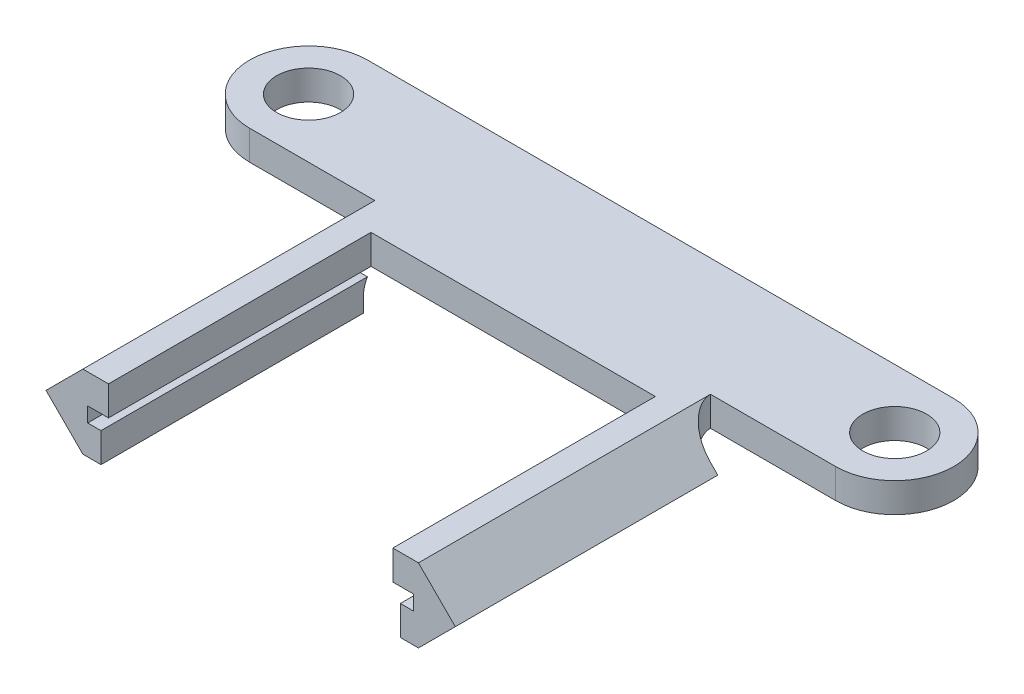
SolidWorks part; units mm, degrees
ref_plane "Front Plane" through (0, 0, 0) normal (0, 0, 1) x (1, 0, 0)
ref_plane "Top Plane" through (0, 0, 0) normal (0, 1, 0) x (1, 0, 0)
ref_plane "Right Plane" through (0, 0, 0) normal (1, 0, 0) x (0, 0, -1)
sketch "Sketch1" plane through (0, 0, 0) normal (0, 0, 1) x (1, 0, 0)
  line L0 (0.8255, 1.27) -> (0, 1.27)
  line L1 (0, 0) -> (0.8255, 0) construction
  line L2 (0, 0) -> (0, 1.27) construction
  line L3 (0, 1.27) -> (0.8255, 1.27) construction
  line L4 (0.8255, 0) -> (0.8255, 1.27) construction
  line L5 (0.4127, 1.27) -> (0.4128, 0) construction
  line L6 (0, 0.635) -> (0.8255, 0.635) construction
  line L7 (0.8255, 0) -> (0, 0)
  line L8 (0, 0) -> (-0.635, 0.635) construction
  line L9 (-0.635, 0.635) -> (0, 1.27) construction
  line L10 (25.9715, 0) -> (26.797, 0)
  line L11 (0.8255, 1.27) -> (25.9715, 1.27)
  line L12 (0.8255, 1.27) -> (0.8255, 0) construction
  line L13 (0.8255, 0) -> (25.9715, 0)
  line L14 (25.9715, 1.27) -> (25.9715, 0) construction
  line L15 (13.3985, 0) -> (13.3985, 1.27) construction
  line L16 (0.8255, 0.635) -> (25.9715, 0.635) construction
  line L17 (26.797, 0) -> (27.432, 0.635) construction
  line L18 (25.9715, 1.27) -> (26.797, 1.27)
  line L19 (27.432, 0.635) -> (26.797, 1.27) construction
  line L20 (-4.2271, 0.635) -> (-1.0521, 3.81)
  line L21 (0.8255, 3.81) -> (-1.0521, 3.81)
  line L22 (0.8255, 3.81) -> (25.9715, 3.81)
  line L23 (25.9715, 3.81) -> (27.8491, 3.81)
  line L24 (31.0241, 0.635) -> (27.8491, 3.81)
  line L25 (27.8491, -2.54) -> (31.0241, 0.635)
  line L26 (25.9715, -2.54) -> (27.8491, -2.54)
  line L27 (0.8255, -2.54) -> (25.9715, -2.54)
  line L28 (0.8255, -2.54) -> (-1.0521, -2.54)
  line L29 (-1.0521, -2.54) -> (-4.2271, 0.635)
  line L30 (0, 1.27) -> (-0.635, 1.27)
  line L31 (-0.635, 1.27) -> (-0.635, 0)
  line L32 (-0.635, 0) -> (0, 0)
  line L33 (26.797, 1.27) -> (27.432, 1.27)
  line L34 (27.432, 1.27) -> (27.432, 0)
  line L35 (27.432, 0) -> (26.797, 0)
  point P287 (13.3985, 0.635)
  point P500 (0.4127, 0.635)
  dimension "D1" = 1.27
  dimension "D2" = 0.8255
  dimension "D3" = 45
  dimension "D4" = 25.146
  dimension "D5" = 2.54
extrude "Boss-Extrude1" add sketch "Sketch1" along normal blind 22.606
sketch "Sketch2" plane through (0, 0, 22.606) normal (0, 0, 1) x (1, 0, 0)
  line L5 (13.3985, 0) -> (13.3985, -2.54) construction
  line L6 (-0.635, 0) -> (27.432, 0) construction
  line L7 (-1.0521, -2.54) -> (27.8491, -2.54) construction
  line L9 (0.508, 0) -> (26.289, 0)
  line L10 (0.508, 0) -> (0.508, -2.54)
  line L11 (0.508, -2.54) -> (26.289, -2.54)
  line L12 (26.289, 0) -> (26.289, -2.54)
  line L13 (13.3985, -2.54) -> (13.3985, 0) construction
  line L14 (0.508, -1.27) -> (26.289, -1.27) construction
  point P218 (13.3985, -1.27)
  dimension "D1" = 0.508
extrude "Cut-Extrude1" cut sketch "Sketch2" against normal blind 22.606
sketch "Sketch5" plane through (0, 0, 0) normal (0, 0, -1) x (-1, 0, 0)
  line L12 (-31.0241, 0.635) -> (-27.432, 0.635)
  line L13 (-27.432, 0.635) -> (-27.432, 1.27)
  line L14 (-27.432, 1.27) -> (0.635, 1.27)
  line L15 (0.635, 1.27) -> (0.635, 0.635)
  line L16 (0.635, 1.27) -> (0.635, 0) construction
  line L17 (0.635, 0.635) -> (4.2271, 0.635)
  line L18 (4.2271, 0.635) -> (1.0521, 3.81)
  line L19 (1.0521, 3.81) -> (-27.8491, 3.81)
  line L20 (-27.8491, 3.81) -> (-31.0241, 0.635)
extrude "Boss-Extrude2" add sketch "Sketch5" along normal blind 12.7
sketch "Sketch3" plane through (0, 3.81, 0) normal (0, 1, 0) x (1, 0, 0)
  line L0 (13.3985, 0) -> (13.3985, -22.606) construction
  line L1 (27.8491, 0) -> (-1.0521, 0) construction
  line L2 (27.8491, -22.606) -> (-1.0521, -22.606) construction
  line L3 (6.1023, -15.0622) -> (2.9845, -15.0622) construction
  line L4 (1.1557, 0) -> (25.6413, 0) construction
  line L5 (1.1557, 0) -> (1.1557, -22.606) construction
  line L6 (1.1557, -22.606) -> (25.6413, -22.606) construction
  line L7 (25.6413, 0) -> (25.6413, -22.606) construction
  line L8 (13.3985, -22.606) -> (13.3985, 0) construction
  line L9 (1.1557, -11.303) -> (25.6413, -11.303) construction
  line L10 (6.1023, 0) -> (20.6947, 0) construction
  line L11 (6.1023, 0) -> (6.1023, -15.0622) construction
  line L12 (6.1023, -15.0622) -> (20.6947, -15.0622) construction
  line L13 (20.6947, 0) -> (20.6947, -15.0622) construction
  line L14 (13.3985, -15.0622) -> (13.3985, 0) construction
  line L15 (6.1023, -7.5311) -> (20.6947, -7.5311) construction
  line L16 (2.9845, 0) -> (23.8125, 0) construction
  line L17 (2.9845, 0) -> (2.9845, -22.606) construction
  line L18 (2.9845, -22.606) -> (23.8125, -22.606) construction
  line L19 (23.8125, 0) -> (23.8125, -22.606) construction
  line L20 (13.3985, -22.606) -> (13.3985, 0) construction
  line L21 (2.9845, -11.303) -> (23.8125, -11.303) construction
  line L22 (2.9845, -15.0622) -> (2.9845, 0) construction
  line L23 (2.9845, 0) -> (1.1557, 0)
  line L24 (1.1557, 0) -> (1.1557, -22.606)
  line L25 (1.1557, -22.606) -> (25.6413, -22.606)
  line L26 (25.6413, -22.606) -> (25.6413, 0)
  line L27 (25.6413, 0) -> (23.8125, 0)
  line L28 (23.8125, 0) -> (23.8125, -15.0622) construction
  line L29 (23.8125, -15.0622) -> (20.6947, -15.0622) construction
  line L32 (6.1023, 0) -> (20.6947, 0)
  line L33 (2.9845, 0) -> (6.1023, 0)
  line L34 (20.6947, 0) -> (23.8125, 0)
  point P250 (13.3985, -11.303)
  point P383 (13.3985, -7.5311)
  point P386 (13.3985, -11.303)
  dimension "D1" = 24.4856
  dimension "D2" = 14.5923
  dimension "D3" = 15.0622
  dimension "D4" = 20.828
extrude "Cut-Extrude4" cut sketch "Sketch3" against normal up to vertex (2.54 mm away)
sketch "Sketch6" plane through (0, 0, -12.7) normal (0, 0, -1) x (-1, 0, 0)
  line L2 (-27.8491, 3.81) -> (-31.0241, 0.635)
  line L3 (-31.0241, 0.635) -> (-27.432, 0.635)
  line L4 (-27.432, 0.635) -> (-27.432, 1.27)
  line L5 (-27.432, 1.27) -> (-27.8491, 1.27)
  line L6 (-27.8491, 1.27) -> (-27.8491, 3.81)
  line L8 (-13.3985, 3.81) -> (-13.3985, 1.27) construction
  line L9 (-0.8255, 3.81) -> (-25.9715, 3.81) construction
  line L11 (1.0521, 1.27) -> (1.0521, 3.81)
  line L12 (0.635, 1.27) -> (1.0521, 1.27)
  line L13 (0.635, 0.635) -> (0.635, 1.27)
  line L14 (4.2271, 0.635) -> (0.635, 0.635)
  line L15 (1.0521, 3.81) -> (4.2271, 0.635)
extrude "Cut-Extrude5" cut sketch "Sketch6" against normal up to surface (12.7 mm away) up to face at (-0.9222, -0.635, 0)
fillet "Fillet1" radius 2.54 8 edges at (27.8491, 2.54, 0) (27.6406, 1.27, 0) (-0.8436, 1.27, 0) (-1.0521, 2.54, 0) (-0.0635, 0, 0) (27.432, 0.635, 0) (26.8605, 0, 0) (-0.635, 0.635, 0)
sketch "Sketch7" plane through (0, 1.27, 0) normal (0, -1, 0) x (1, 0, 0)
  line L2 (13.3985, 0) -> (13.3985, -12.7) construction
  line L3 (25.6413, 0) -> (1.1557, 0) construction
  line L4 (27.8491, -12.7) -> (-1.0521, -12.7) construction
  line L5 (-1.0521, -7.62) -> (27.8491, -7.62) construction
  line L6 (-1.0521, -2.54) -> (-1.0521, -12.7) construction
  line L7 (27.8491, -2.54) -> (27.8491, -12.7) construction
  line L8 (-1.0521, -7.62) -> (-11.8415, -7.62) construction
  line L9 (-1.0521, -2.54) -> (-11.8415, -2.54)
  line L10 (-1.0521, -2.54) -> (27.8491, -2.54)
  line L11 (27.8491, -2.54) -> (38.6385, -2.54)
  line L12 (27.8491, -12.7) -> (38.6385, -12.7)
  line L13 (-1.0521, -12.7) -> (27.8491, -12.7)
  line L14 (-1.0521, -12.7) -> (-11.8415, -12.7)
  line L15 (-11.8415, -2.54) -> (-11.8415, -12.7) construction
  circle A4 centre (-11.8415, -7.62) radius 2 construction
  circle A5 centre (38.6385, -7.62) radius 2 construction
  arc A6 (-11.8415, -12.7) -> (-11.8415, -2.54) centre (-11.8415, -7.62) cw
  arc A7 (38.6385, -12.7) -> (38.6385, -2.54) centre (38.6385, -7.62) ccw
  dimension "D1" = 50.48
  dimension "D2" = 4
extrude "Boss-Extrude3" add sketch "Sketch7" against normal up to surface (2.54 mm away) up to face at (13.3985, 3.81, 5.9944)
hole_wizard "M5 Clearance Hole1" positions "Sketch8" profile "Sketch9" hole size "M5" standard "ANSI Metric" end condition through all
sketch "Sketch8" plane through (0, 1.27, 0) normal (0, -1, 0) x (-1, 0, 0)
  point P6 (-38.6385, 7.62)
  point P10 (11.8415, 7.62)
sketch "Sketch9" plane through (38.6385, 1.27, -7.62) normal (1, 0, 0) x (0, 0, -1)
  line L0 (0, 0) -> (0, 2.54)
  line L1 (0, 2.54) -> (2.75, 2.54)
  line L2 (2.75, 2.54) -> (2.75, 0)
  line L5 (2.75, 0) -> (0, 0)
  line L11 (0, -6.35) -> (0, 107.95) construction
  dimension "Thru Hole Dia." = 5.5
  dimension "Thru Hole Depth" = 2.54
